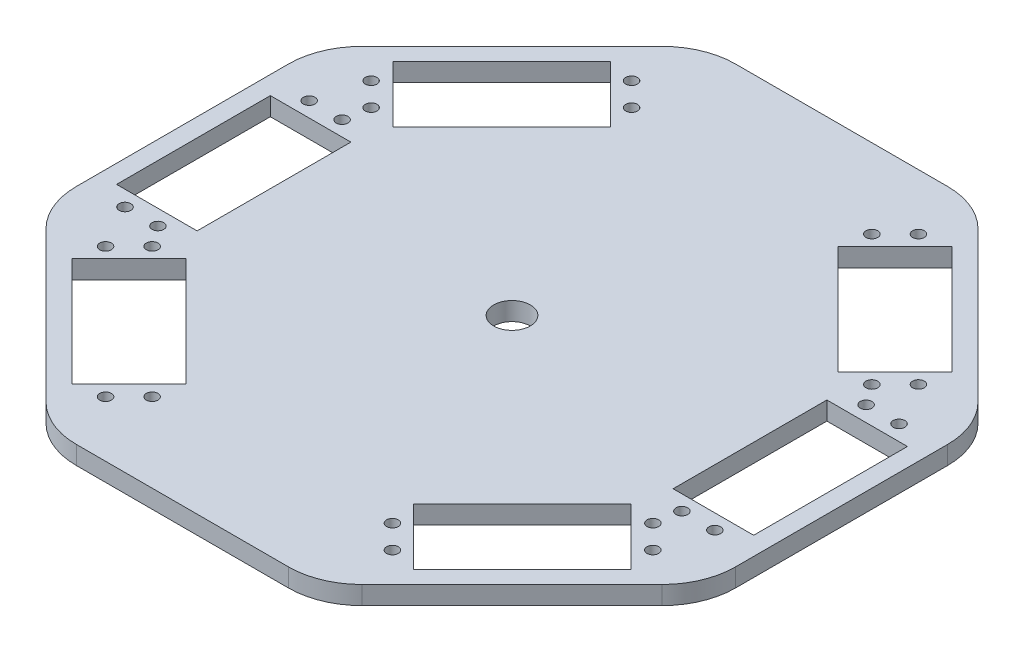
SolidWorks part; units mm, degrees
ref_plane "Front Plane" through (0, 0, 0) normal (0, 0, 1) x (1, 0, 0)
ref_plane "Top Plane" through (0, 0, 0) normal (0, 1, 0) x (1, 0, 0)
ref_plane "Right Plane" through (0, 0, 0) normal (1, 0, 0) x (0, 0, -1)
sketch "Sketch1" plane through (0, 0, 0) normal (0, 1, 0) x (1, 0, 0)
  line L1 (-90, -37.2792) -> (-37.2792, -90)
  line L2 (-37.2792, -90) -> (37.2792, -90)
  line L3 (37.2792, -90) -> (90, -37.2792)
  line L4 (90, -37.2792) -> (90, 37.2792)
  line L5 (90, 37.2792) -> (37.2792, 90)
  line L6 (37.2792, 90) -> (-37.2792, 90)
  line L7 (-37.2792, 90) -> (-90, 37.2792)
  line L8 (-90, 37.2792) -> (-90, -37.2792)
  line L12 (63.6396, -63.6396) -> (0, 0) construction
  line L21 (-20.4, -34.5422) -> (-34.5422, -20.4)
  line L22 (-20.4, -34.5422) -> (-50.0985, -64.2407)
  line L23 (-50.0985, -64.2407) -> (-64.2407, -50.0985)
  line L24 (-34.5422, -20.4) -> (-64.2407, -50.0985)
  line L25 (-38.85, -10) -> (-38.85, 10)
  line L26 (-38.85, -10) -> (-80.85, -10)
  line L27 (-80.85, -10) -> (-80.85, 10)
  line L28 (-38.85, 10) -> (-80.85, 10)
  line L29 (-34.5422, 20.4) -> (-20.4, 34.5422)
  line L30 (-34.5422, 20.4) -> (-64.2407, 50.0985)
  line L31 (-64.2407, 50.0985) -> (-50.0985, 64.2407)
  line L32 (-20.4, 34.5422) -> (-50.0985, 64.2407)
  line L37 (20.4, 34.5422) -> (34.5422, 20.4)
  line L38 (20.4, 34.5422) -> (50.0985, 64.2407)
  line L39 (50.0985, 64.2407) -> (64.2407, 50.0985)
  line L40 (34.5422, 20.4) -> (64.2407, 50.0985)
  line L41 (38.85, 10) -> (38.85, -10)
  line L42 (38.85, 10) -> (80.85, 10)
  line L43 (80.85, 10) -> (80.85, -10)
  line L44 (38.85, -10) -> (80.85, -10)
  circle A0 centre (0, 0) radius 90 construction
  circle A13 centre (0, 0) radius 90 construction
  circle A14 centre (-27.7186, -21.3546) radius 2.5
  circle A15 centre (-21.3546, -27.7186) radius 2.5
  circle A16 centre (-56.9221, -63.2861) radius 2.5
  circle A17 centre (-63.2861, -56.9221) radius 2.5
  circle A18 centre (0, 0) radius 90 construction
  circle A19 centre (-34.7, 4.5) radius 2.5
  circle A20 centre (-34.7, -4.5) radius 2.5
  circle A21 centre (-85, -4.5) radius 2.5
  circle A22 centre (-85, 4.5) radius 2.5
  circle A23 centre (0, 0) radius 90 construction
  circle A24 centre (-21.3546, 27.7186) radius 2.5
  circle A25 centre (-27.7186, 21.3546) radius 2.5
  circle A26 centre (-63.2861, 56.9221) radius 2.5
  circle A27 centre (-56.9221, 63.2861) radius 2.5
  circle A28 centre (0, 0) radius 90 construction
  circle A33 centre (0, 0) radius 90 construction
  circle A34 centre (27.7186, 21.3546) radius 2.5
  circle A35 centre (21.3546, 27.7186) radius 2.5
  circle A36 centre (56.9221, 63.2861) radius 2.5
  circle A37 centre (63.2861, 56.9221) radius 2.5
  circle A38 centre (0, 0) radius 90 construction
  circle A39 centre (34.7, -4.5) radius 2.5
  circle A40 centre (34.7, 4.5) radius 2.5
  circle A41 centre (85, 4.5) radius 2.5
  circle A42 centre (85, -4.5) radius 2.5
  circle A43 centre (0, 0) radius 90 construction
  point P15 (63.6396, -63.6396)
  point P16 (60.1041, -60.1041)
  point P17 (57.1696, -57.1696)
  point P121 (0, 0)
  dimension "D1" = 90
  dimension "D12" = 8
extrude "Boss-Extrude1" add sketch "Sketch1" along normal blind 5 contours L7 L8 L1 L2 L3 L4 L5 L6 A42 A41 A40 A39 A37 A36 A35 A34 A27 A26 A25 A24 A22 A21 A20 A19 A17 A16 A15 A14 L44 L41 | L29 L32 L31 L30 | L37 L40 L39 L38 | L41 L44 L43 L42 | L25 L28 L27 L26 | A27 | A26 | A25 | A24 | A22 | A21 | A19 | A20 | A14 | A15 | A17 | A16 | A40 | A41 | A42 | A35 | A34 | A39 | A37 | A36 | L21 L24 L23 L22 region at (1.7472, 0, 1.7472) region at (-59.85, 0, 0) region at (-42.3203, 0, -42.3203) region at (42.3203, 0, -42.3203) region at (59.85, 0, 0) region at (-27.7186, 0, 21.3546) region at (-21.3546, 0, 27.7186) region at (-56.9221, 0, 63.2861) region at (-63.2861, 0, 56.9221) region at (-34.7, 0, -4.5) region at (-34.7, 0, 4.5) region at (-85, 0, 4.5) region at (-85, 0, -4.5) region at (-21.3546, 0, -27.7186) region at (-27.7186, 0, -21.3546) region at (-63.2861, 0, -56.9221) region at (-56.9221, 0, -63.2861) region at (34.7, 0, -4.5) region at (85, 0, -4.5) region at (85, 0, 4.5)
fillet "Fillet1" radius 20 8 edges at (-90, 2.5, -37.2792) (-37.2792, 2.5, -90) (37.2792, 2.5, -90) (90, 2.5, -37.2792) (90, 2.5, 37.2792) (37.2792, 2.5, 90) (-37.2792, 2.5, 90) (-90, 2.5, 37.2792)
sketch "Sketch2" plane through (0, 5, 0) normal (0, 1, 0) x (1, 0, 0)
  line L0 (90, -28.9949) -> (90, 28.9949) construction
  line L1 (63, 23.0051) -> (85, 23.0051)
  line L2 (63, 23.0051) -> (63, -18.9949)
  line L3 (63, -18.9949) -> (85, -18.9949)
  line L4 (85, 23.0051) -> (85, -18.9949)
  circle A0 centre (78.5, 27.2051) radius 1.6
  circle A1 centre (69.5, 27.2051) radius 1.6
  circle A2 centre (69.5, -23.0949) radius 1.6
  circle A3 centre (78.5, -23.0949) radius 1.6
  point P8 (74, 23.0051)
  dimension "D1" = 3.2
  dimension "D2" = 9
  dimension "D3" = 50.3
  dimension "D4" = 22
  dimension "D5" = 42
  dimension "D6" = 4.2
  dimension "D7" = 4.5
  dimension "D8" = 5
  dimension "D9" = 10
extrude "Cut-Extrude1" cut sketch "Sketch2" against normal through all contours A0 | L4 L1 L2 L3 | A2 | A3 | A1 region at (74, 5, -2.0051) region at (78.5, 5, -27.2051) region at (69.5, 5, 23.0949) region at (78.5, 5, 23.0949)
sketch "Sketch3" plane through (0, 5, 0) normal (0, 1, 0) x (1, 0, 0)
  circle A0 centre (0, 0) radius 5
  dimension "D1" = 10
extrude "Cut-Extrude2" cut sketch "Sketch3" against normal through all
pattern_circular "CirPattern1" count 8 over 360 about axis through (0, 5, 0) along (0, 1, 0) skipping 2, 6 of "Cut-Extrude1"
